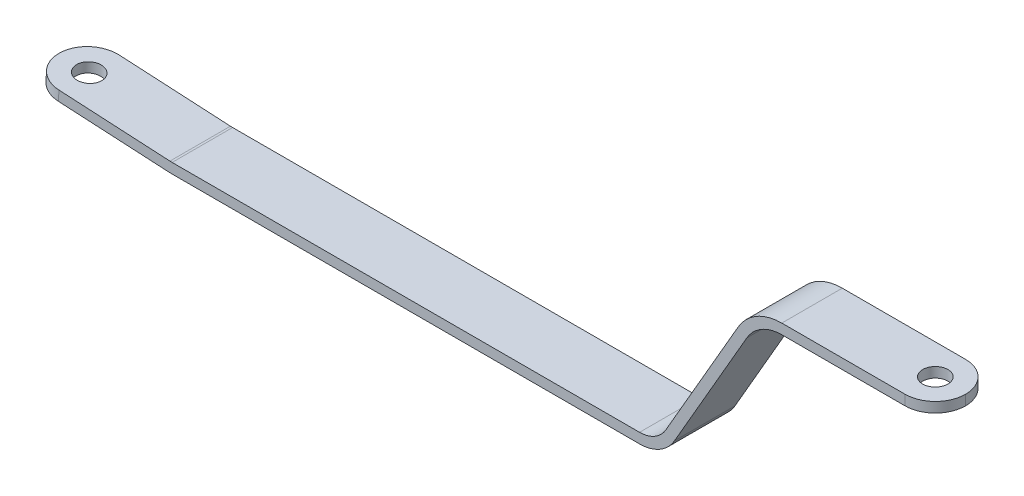
SolidWorks part; units mm, degrees
ref_plane "Front Plane" through (0, 0, 0) normal (0, 0, 1) x (1, 0, 0)
ref_plane "Top Plane" through (0, 0, 0) normal (0, 1, 0) x (1, 0, 0)
ref_plane "Right Plane" through (0, 0, 0) normal (1, 0, 0) x (0, 0, -1)
sketch "Sketch1" plane through (0, 0, 0) normal (0, 0, 1) x (1, 0, 0)
  line L0 (0, 0) -> (14.0045, -0.7609)
  line L1 (14.2757, -0.7683) -> (60.65, -0.7683)
  line L2 (64.1141, 1.2317) -> (71.2963, 13.6717)
  line L3 (74.7604, 15.6717) -> (89.99, 15.6717)
  arc A0 (60.65, -0.7683) -> (64.1141, 1.2317) centre (60.65, 3.2317) ccw
  arc A1 (14.0045, -0.7609) -> (14.2757, -0.7683) centre (14.2757, 4.2317) ccw
  arc A2 (71.2963, 13.6717) -> (74.7604, 15.6717) centre (74.7604, 11.6717) cw
  point P10 (14.14, -0.7683)
  point P13 (72.451, 15.6717)
  dimension "D4" = 4
  dimension "D8" = 5
  dimension "D9" = 4
  dimension "D1" = 3.11
  dimension "D2" = 46.51
  dimension "D3" = 14.14
  dimension "D5" = 60
  dimension "D6" = 16.44
  dimension "D7" = 89.99
extrude "Extrude-Thin1" add sketch "Sketch1" along normal mid plane 6 thin thin type one direction reverse wall 1
sketch "Sketch2" plane through (0.0543, 0.9985, 0) normal (0.0543, 0.9985, 0) x (0.9985, -0.0543, 0)
  circle A0 centre (3, 0) radius 1.25
  dimension "D1" = 2.5
  dimension "D2" = 3
extrude "Cut-Extrude1" cut sketch "Sketch2" against normal up to next
sketch "Sketch3" plane through (0, 16.6717, 0) normal (0, 1, 0) x (1, 0, 0)
  line L0 (89.99, -3) -> (89.99, 3) construction
  circle A0 centre (86.99, 0) radius 1.25
  point P2 (89.99, 0)
  dimension "D1" = 3
  dimension "D2" = 2.5
extrude "Cut-Extrude2" cut sketch "Sketch3" against normal up to next
fillet "Fillet1" radius 3 4 edges at (0.0271, 0.4993, -3) (0.0271, 0.4993, 3) (89.99, 16.1717, -3) (89.99, 16.1717, 3)
